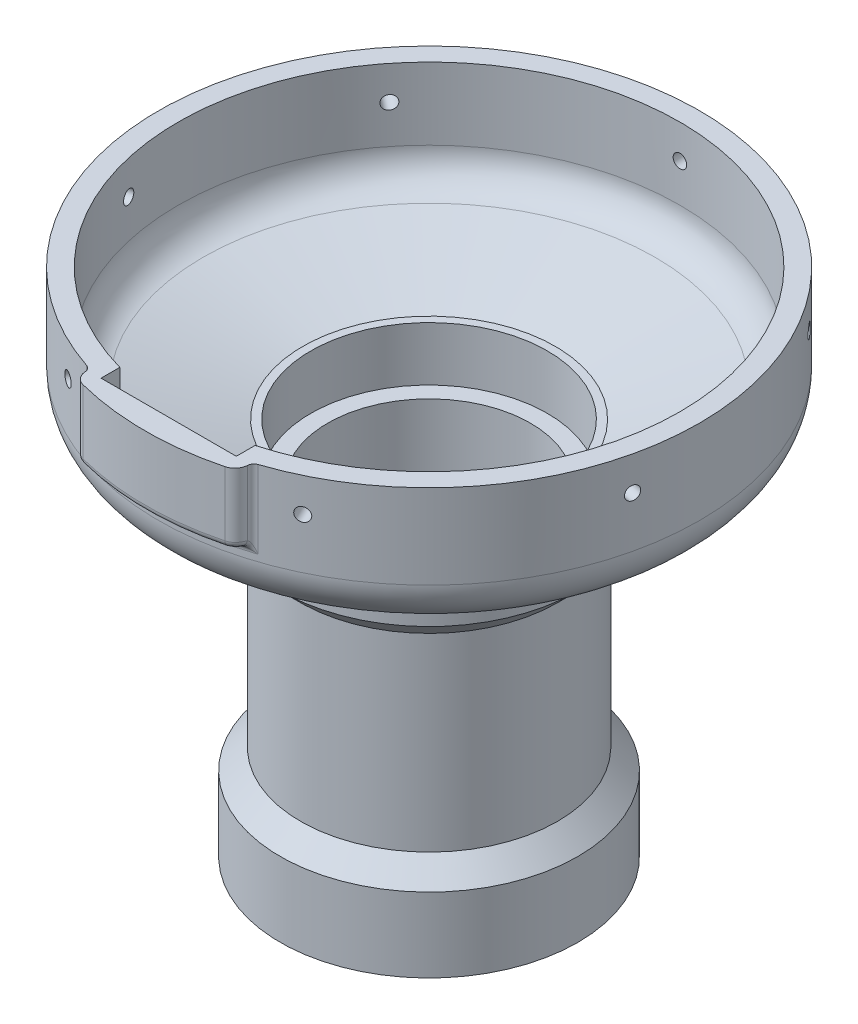
SolidWorks part; units mm, degrees
material "ПК/АБС"
ref_plane "Спереди" through (0, 0, 0) normal (0, 0, 1) x (1, 0, 0)
ref_plane "Сверху" through (0, 0, 0) normal (0, 1, 0) x (1, 0, 0)
ref_plane "Справа" through (0, 0, 0) normal (1, 0, 0) x (0, 0, -1)
sketch "Эскиз1" plane through (0, 0, 0) normal (0, 0, 1) x (1, 0, 0)
  line L0 (-15.4514, 14.249) -> (-15.4514, 36.749) construction
  line L1 (21.6486, 38.751) -> (24.5486, 38.751)
  line L2 (3.5486, 5.249) -> (6.5486, 8.249)
  line L3 (24.5486, 38.751) -> (24.5486, 26.2739)
  line L4 (6.5486, 8.249) -> (6.5486, 10.6688)
  line L5 (3.5486, 5.249) -> (3.5486, -22.751)
  line L6 (6.5486, -36.751) -> (2.0486, -36.751)
  line L7 (2.0486, -36.751) -> (2.0486, -28.751)
  line L8 (2.0486, -28.751) -> (-0.4514, -28.751)
  line L9 (-0.4514, -28.751) -> (-0.4514, 11.249)
  line L10 (-0.4514, 11.249) -> (2.0486, 11.249)
  line L11 (2.0486, 11.249) -> (2.0486, 19.249)
  line L12 (11.7044, 17.4215) -> (19.3928, 19.5212)
  line L14 (21.6486, 38.751) -> (21.6486, 28.1013)
  line L15 (17.9658, 23.278) -> (3.2131, 19.249)
  line L16 (2.0486, 19.249) -> (3.2131, 19.249)
  line L17 (6.5486, -25.751) -> (6.5486, -36.751)
  line L18 (6.5486, -25.751) -> (3.5486, -22.751)
  arc A0 (17.9658, 23.278) -> (21.6486, 28.1013) centre (16.6486, 28.1013) ccw
  arc A1 (6.5486, 10.6688) -> (11.7044, 17.4215) centre (13.5486, 10.6688) cw
  arc A2 (19.3928, 19.5212) -> (24.5486, 26.2739) centre (17.5486, 26.2739) ccw
  point P20 (3.5486, 9.249)
  dimension "D5" = 5
  dimension "D7" = 7
  dimension "D8" = 7
  dimension "D1" = 2.9
  dimension "D2" = 4
  dimension "D3" = 40
  dimension "D4" = 21
  dimension "D6" = 4
  dimension "D9" = 17.5
  dimension "D10" = 40
  dimension "D11" = 8
  dimension "D12" = 8
  dimension "D13" = 22
  dimension "D14" = 11
  dimension "D15" = 45
  dimension "D16" = 15.275
  dimension "D17" = 19.502
revolve "Повернуть1" add sketch "Эскиз1" angle 360 about L0
sketch "Эскиз2" plane through (0, 38.751, 0) normal (0, 1, 0) x (1, 0, 0)
  line L0 (-15.4514, 0) -> (-15.4514, -56.249) construction
  line L1 (-25.4514, -38.5) -> (-5.4514, -38.5)
  line L2 (-25.4514, -38.5) -> (-25.4514, -30.7161)
  line L3 (-25.4514, -30.7161) -> (-5.4514, -30.7161)
  line L4 (-5.4514, -30.7161) -> (-5.4514, -38.5)
  dimension "D1" = 38.5
  dimension "D2" = 10
  dimension "D3" = 10
extrude "Вырез-Вытянуть1" cut sketch "Эскиз2" against normal blind 9
sketch "Эскиз3" plane through (0, 38.751, 0) normal (0, 1, 0) x (1, 0, 0)
  line L0 (-27.4514, -38.7298) -> (-27.4514, -38.1576)
  line L1 (-3.4514, -38.7298) -> (-3.4514, -38.1576)
  line L2 (-25.4514, -35.7269) -> (-25.4514, -38.5) construction
  line L3 (-5.4514, -38.5) -> (-5.4514, -35.7269) construction
  arc A0 (-25.9514, -40.6663) -> (-4.9514, -40.6663) centre (-15.4514, 0) ccw
  arc A1 (-27.4514, -38.1576) -> (-3.4514, -38.1576) centre (-15.4514, 0) ccw
  arc A2 (-25.9514, -40.6663) -> (-27.4514, -38.7298) centre (-25.4514, -38.7298) cw
  arc A3 (-4.9514, -40.6663) -> (-3.4514, -38.7298) centre (-5.4514, -38.7298) ccw
  dimension "D1" = 2
  dimension "D3" = 2
  dimension "D2" = 2
extrude "Бобышка-Вытянуть1" add sketch "Эскиз3" against normal blind 10.5
fillet "Скругление1" radius 1 3 edges at (-3.4514, 33.501, 38.1576) (-27.4514, 33.501, 38.1576) (-15.4514, 28.251, 40)
fillet "Скругление2" radius 1 5 edges at (-27.7029, 27.7508, 38.2182) (-3.2, 27.7508, 38.2182) (-15.4514, 28.251, 42)
ref_plane "Плоскость1" through (0, 0, -40) normal (0, 0, 1) x (1, 0, 0)
sketch "Эскиз4" plane through (0, 0, -40) normal (0, 0, 1) x (1, 0, 0)
  line L0 (-15.4514, 59.2828) -> (-15.4514, -45.5652) construction
  line L1 (24.5486, 38.751) -> (-55.4514, 38.751) construction
  circle A0 centre (-15.4514, 33.751) radius 1
  dimension "D1" = 2
  dimension "D2" = 5
extrude "Вырез-Вытянуть2" cut sketch "Эскиз4" along normal blind 10.5 contours A0
pattern_circular "Круговой массив1" count 7 over 360 about axis through (-15.4514, 14.249, 0) along (0, -1, 0) of "Вырез-Вытянуть2"
